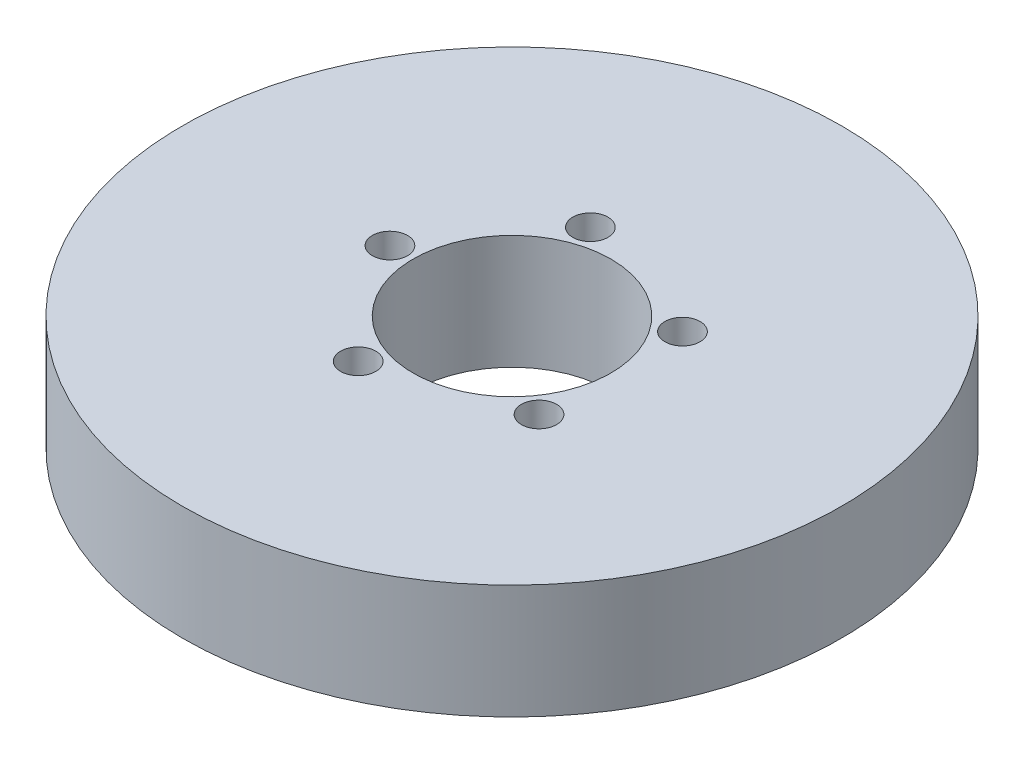
SolidWorks part; units mm, degrees
ref_plane "Front Plane" through (0, 0, 0) normal (0, 0, 1) x (1, 0, 0)
ref_plane "Top Plane" through (0, 0, 0) normal (0, 1, 0) x (1, 0, 0)
ref_plane "Right Plane" through (0, 0, 0) normal (1, 0, 0) x (0, 0, -1)
sketch "Sketch1" plane through (0, 0, 0) normal (0, 1, 0) x (1, 0, 0)
  circle A0 centre (0, 0) radius 75
  dimension "FLANGE_OD" = 150
extrude "Boss-Extrude1" add sketch "Sketch1" along normal blind 26
sketch "Sketch2" plane through (0, 0, 0) normal (0, 1, 0) x (1, 0, 0)
  circle A0 centre (0, 0) radius 22.5
  dimension "BORE_D" = 45
extrude "Cut-Extrude1" cut sketch "Sketch2" along normal through all
sketch "Sketch3" plane through (0, 26, 0) normal (0, 1, 0) x (1, 0, 0)
  circle A0 centre (0, 0) radius 27.7763 construction
  circle A1 centre (-27.7763, 0) radius 4.0047
  dimension "BOLT_D" = 8.0094
  dimension "BOLT_PCD" = 55.5526
extrude "Cut-Extrude2" cut sketch "Sketch3" against normal blind 16.5104
pattern_circular "CirPattern1" count 5 over 360 about axis through (0, 0, 0) along (0, 1, 0) of "Cut-Extrude2"
